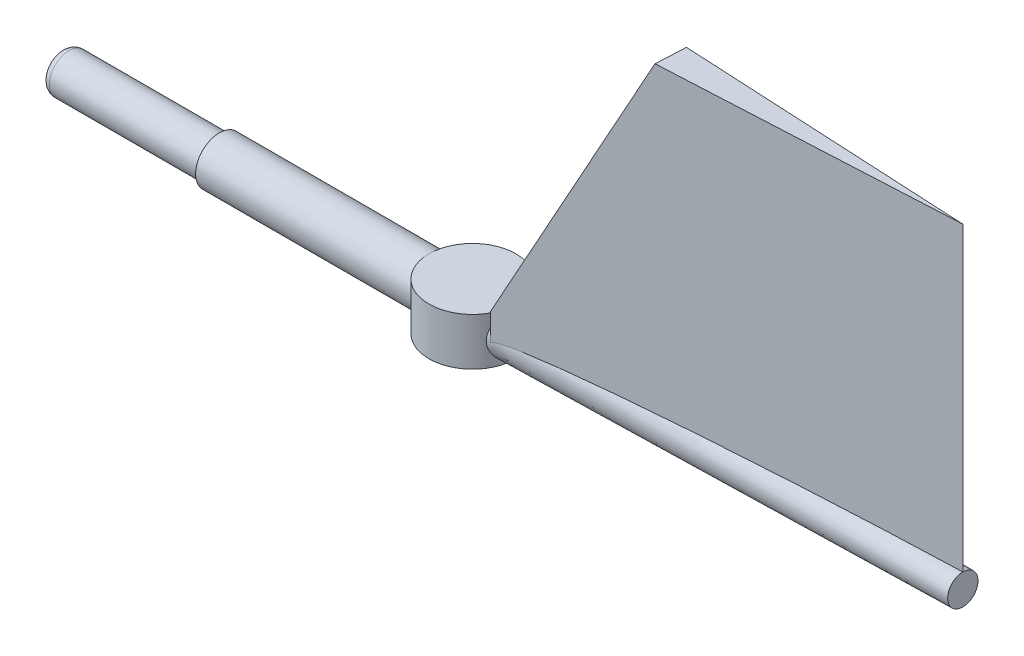
SolidWorks part; units mm, degrees
ref_plane "Front Plane" through (0, 0, 0) normal (0, 0, 1) x (1, 0, 0)
ref_plane "Top Plane" through (0, 0, 0) normal (0, 1, 0) x (1, 0, 0)
ref_plane "Right Plane" through (0, 0, 0) normal (1, 0, 0) x (0, 0, -1)
sketch "Sketch1" plane through (0, 0, 0) normal (0, 1, 0) x (1, 0, 0)
  circle A0 centre (0, 0) radius 27.5
  dimension "D1" = 55
extrude "Boss-Extrude1" add sketch "Sketch1" along normal blind 30
sketch "Sketch2" plane through (0, 0, 0) normal (0, -1, 0) x (1, 0, 0)
  circle A0 centre (0, 0) radius 25
  dimension "D1" = 50
sketch "Sketch4" plane through (0, 0, 0) normal (1, 0, 0) x (0, 0, -1)
  line L2 (-27.5, 0) -> (27.5, 0) construction
  line L3 (27.5, 0) -> (27.5, 30) construction
  circle A0 centre (0, 15) radius 15
  dimension "D1" = 15
  dimension "D2" = 30
  dimension "D3" = 27.5
extrude "Boss-Extrude3" add sketch "Sketch4" along normal blind 310 draft 1 and the other way blind 160
sketch "Sketch5" plane through (-160, 0, 0) normal (-1, 0, 0) x (0, 0, 1)
  circle A0 centre (0, 15) radius 12.5
  dimension "D1" = 25
extrude "Boss-Extrude4" add sketch "Sketch5" along normal blind 100
fillet "Fillet1" radius 5 1 edges at (-260, 15, 12.5)
ref_plane "Plane1" through (0, 15, 0) normal (0, 1, 0) x (1, 0, 0)
sketch "Sketch7" plane through (0, 15, 0) normal (0, 1, 0) x (1, 0, 0)
  line L0 (26, -14.5462) -> (26, 14.5462)
  line L1 (23.3086, -14.5931) -> (310, -9.5889) construction
  line L2 (310, 9.5889) -> (23.3086, 14.5931) construction
  line L3 (26, 14.5462) -> (310, 0)
  line L4 (310, 0) -> (26, -14.5462)
  line L5 (310, -9.5889) -> (310, 9.5889) construction
  circle A0 centre (0, 0) radius 27.5 construction
  dimension "D1" = 284
  dimension "D2" = 0
  dimension "D3" = 26
  dimension "D4" = 9.5875
  dimension "D5" = 9.5875
extrude "Boss-Extrude5" add sketch "Sketch7" along normal blind 200
extrude "Cut-Extrude4" cut sketch "Sketch2" against normal blind 20
sketch "Sketch9" plane through (0.8111, 0, -15.8363) normal (0.0512, 0, -0.9987) x (-0.9987, 0, -0.0512)
  line L0 (-25.2219, 29.7622) -> (-125.2219, 215)
  line L1 (-25.2219, 215) -> (-25.2219, 15) construction
  line L2 (-309.5942, 215) -> (-25.2219, 215) construction
  line L3 (-125.2219, 215) -> (-25.2219, 215)
  line L4 (-25.2219, 215) -> (-25.2219, 29.7622)
  dimension "D1" = 100
extrude "Cut-Extrude6" cut sketch "Sketch9" against normal blind 50
